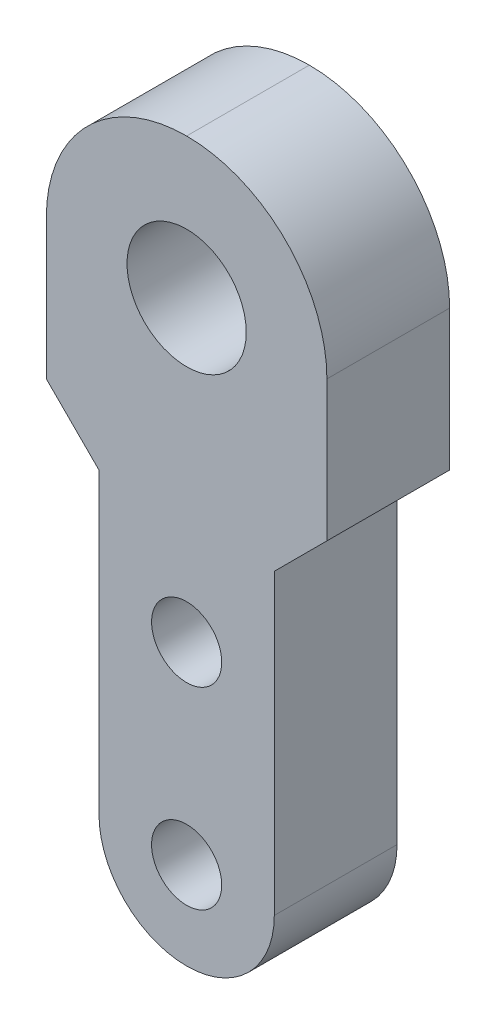
SolidWorks part; units mm, degrees
ref_plane "Front" through (0, 0, 0) normal (0, 0, 1) x (1, 0, 0)
ref_plane "Top" through (0, 0, 0) normal (0, 1, 0) x (1, 0, 0)
ref_plane "Right" through (0, 0, 0) normal (1, 0, 0) x (0, 0, -1)
sketch "Esquisse1" plane through (0, 0, 0) normal (0, 0, 1) x (1, 0, 0)
  line L1 (0, 0) -> (10, 0)
  line L2 (0, 0) -> (0, 25)
  line L3 (0, 25) -> (10, 25)
  line L4 (10, 0) -> (10, 25)
  dimension "D1" = 10
  dimension "D2" = 25
extrude "Boss.-Extru.1" add sketch "Esquisse1" along normal blind 7
sketch "Esquisse2" plane through (0, 0, 7) normal (0, 0, 1) x (1, 0, 0)
  line L0 (5, 25) -> (5, 41) construction
  line L1 (10, 25) -> (0, 25) construction
  line L2 (13, 41) -> (-3, 41)
  line L3 (-3, 41) -> (-3, 25)
  line L4 (-3, 25) -> (13, 25)
  line L5 (13, 41) -> (13, 25)
  dimension "D1" = 16
  dimension "D2" = 16
extrude "Boss.-Extru.2" add sketch "Esquisse2" against normal up to vertex (7 mm away) up to point (10, 0, 0)
sketch "Esquisse3" plane through (0, 0, 7) normal (0, 0, 1) x (1, 0, 0)
  line L0 (5, 41) -> (5, 25) construction
  line L1 (13, 41) -> (-3, 41) construction
  line L2 (5, 25) -> (0, 25) construction
  line L3 (5, 0) -> (5, 16) construction
  line L4 (0, 0) -> (10, 0) construction
  circle A0 centre (5, 33) radius 3.4
  circle A1 centre (5, 16) radius 2
  circle A2 centre (5, 5) radius 2
  dimension "D1" = 6.8
  dimension "D2" = 4
  dimension "D3" = 11
  dimension "D4" = 5
extrude "Enlèv. mat.-Extru.1" cut sketch "Esquisse3" against normal through all
fillet "Congé1" radius 8 2 edges at (13, 41, 3.5) (-3, 41, 3.5)
chamfer "Chanfrein1" distance 3 angle 45 2 edges at (10, 25, 3.5) (0, 25, 3.5)
fillet "Congé2" radius 5 2 edges at (10, 0, 3.5) (0, 0, 3.5)
